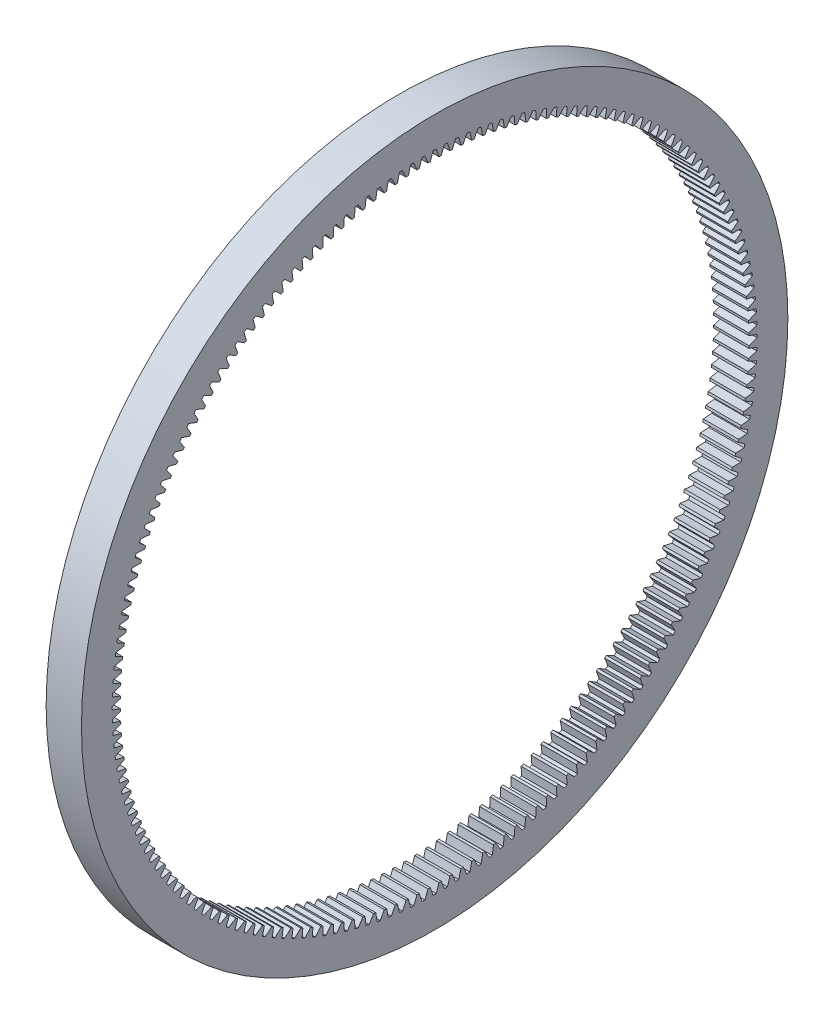
SolidWorks part; units mm, degrees
ref_plane "Plane1" through (0, 0, 0) normal (0, 0, 1) x (1, 0, 0)
ref_plane "Plane2" through (0, 0, 0) normal (0, 1, 0) x (1, 0, 0)
ref_plane "Plane3" through (0, 0, 0) normal (1, 0, 0) x (0, 0, -1)
other "Configuration Table"
sketch "HoldingSke" plane through (0, 0, 0) normal (0, 1, 0) x (1, 0, 0)
  line L0 (0, 0) -> (-1016, 0)
  line L1 (-15, 0) -> (100, 0) construction
  line L2 (0, 0) -> (-2.1039, 2.3779)
  line L3 (0, 0) -> (-11.863, 4.5341)
  line L4 (0, 0) -> (-8.636, 0)
  line L5 (0, 0) -> (-23.7986, -8.8762)
  line L6 (0, 0) -> (-10.5278, -7.1032)
  line L7 (-2.1039, 2.3779) -> (3.3635, 27.1825)
  line L8 (-76.2, 54.61) -> (-54.61, 54.61)
  line L9 (-71.009, 38.7566) -> (-53.1078, 45.2721)
  line L10 (-76.2, 71.12) -> (104.1128, 71.12)
  line L11 (0, 0) -> (-6.35, 0)
  line L12 (-76.2, 101.6) -> (-76.1746, 101.6)
  line L13 (24.9733, 27.94) -> (52.9518, 28.4284)
  line L14 (24.9733, 27.94) -> (25.0241, 27.9398)
  line L15 (24.9733, 27.94) -> (100.4021, 29.52)
  circle A0 centre (0, 0) radius 63.5
  circle A1 centre (0, 0) radius 12.7
  circle A2 centre (0, 0) radius 12.7
  dimension "Num_teeth" = 180
  dimension "Pitch_radius" = 180.3128
  dimension "Width" = 6.35
  dimension "Diameter" = 127
sketch "BasProSke" plane through (0, 0, 0) normal (0, 1, 0) x (1, 0, 0)
  line L0 (-10, 0) -> (60, 0) construction
  line L1 (0, 56.515) -> (0, 63.5)
  line L2 (0, 56.515) -> (6.35, 56.515)
  line L3 (6.35, 56.515) -> (6.35, 63.5)
  line L4 (6.35, 63.5) -> (0, 63.5)
  dimension "Thickness" = 6.35
  dimension "Diameter" = 127
revolve "Base-Revolve" add sketch "BasProSke" angle 360 about L0
sketch "TooCutSke" plane through (0, 0, 0) normal (1, 0, 0) x (0, 0, -1)
  line L3 (0.5622, 57.1472) -> (0.5622, 53.6633) construction
  line L4 (0, 0) -> (0, 59.563) construction
  line L5 (0, 0) -> (-1.1925, 68.3171) construction
  line L6 (-26.4678, 47.8785) -> (36.9935, 48.9862) construction
  circle A0 centre (0, 0) radius 57.15 construction
  circle A1 centre (0, 0) radius 57.9628 construction
  circle A2 centre (0, 0) radius 48.3331 construction
  circle A3 centre (0, 0) radius 56.4896 construction
  arc A4 (0.7806, 56.4842) -> (0.2689, 57.9622) centre (-26.4678, 47.8785) ccw
  arc A5 (0.7806, 56.4842) -> (-0.7806, 56.4842) centre (0, 0) ccw
  arc A6 (0.2689, 57.9622) -> (-0.2689, 57.9622) centre (0, 0) ccw
  arc A7 (-0.2689, 57.9622) -> (-0.7806, 56.4842) centre (26.4678, 47.8785) ccw
extrude "ToothCut" cut sketch "TooCutSke" along normal through all
fillet "Breaks" [suppressed] radius 0.0635
fillet "RootFillets" [suppressed] radius 0.1778
pattern_circular "TeethCuts" count 180 every 2 about axis through (-10, 0, 0) along (1, 0, 0) of "RootFillets", "Breaks", "ToothCut"
equation "' \"Pitch@HoldingSke\" = 4"
equation "' \"Num_teeth@HoldingSke\" = 24"
equation "' \"Ap@HoldingSke\" =  14.5"
equation "' \"Ap@HoldingSke\" = 14.5"
equation "' \"Width@HoldingSke\" = 0.5"
equation "' \"Diameter@HoldingSke\" = 8"
equation "' \"Show_teeth@HoldingSke\" = 100"
equation "' \"Backlash@HoldingSke\" = 0.009"
equation "' \"Addendum_fac@HoldingSke\" = 1.0"
equation "' \"Dedendum_fac@HoldingSke\" = 1.25"
equation "' \"Dedendum_add@HoldingSke\" = 0.00005"
equation "' \"Clearance_fac@HoldingSke\" = 0.25"
equation "\"Overcut_dia@TooCutSke\" = (\"Num_teeth@HoldingSke\" - 2 * \"Addendum_fac@HoldingSke\") / \"Pitch@HoldingSke\" - 0.002"
equation "\"Pitch_dia@TooCutSke\" = \"Num_teeth@HoldingSke\" / \"Pitch@HoldingSke\""
equation "\"Base_dia@TooCutSke\" = \"Num_teeth@HoldingSke\" / \"Pitch@HoldingSke\" * cos((\"Ap@HoldingSke\"  * 3.14159265 / 180)) * 0.90"
equation "\"Root_dia@TooCutSke\" = \"Num_teeth@HoldingSke\"  / \"Pitch@HoldingSke\" + 2 *  \"Dedendum_fac@HoldingSke\"/ \"Pitch@HoldingSke\" + \"Dedendum_add@HoldingSke\" * 2"
equation "\"Half_ang@TooCutSke\" = 180 / \"Num_teeth@HoldingSke\""
equation "\"Half_CT@TooCutSke\" = \"Num_teeth@HoldingSke\" / \"Pitch@HoldingSke\" * sin((3.14159265 / 2 / \"Num_teeth@HoldingSke\")) / 2 + 10 * \"Backlash@HoldingSke\" / 4"
equation "\"Flank_rad@TooCutSke\" = \"Num_teeth@HoldingSke\" / \"Pitch@HoldingSke\" / 4"
equation "\"Radius@RootFillets\"= \"Clearance_fac@HoldingSke\" / \"Pitch@HoldingSke\" + \"Dedendum_add@HoldingSke\""
equation "\"Break_rad@Breaks\" = 0.02 / \"Pitch@HoldingSke\" * 5"
equation "\"Num_teeth@TeethCuts\" = int( \"Show_teeth@HoldingSke\" ) + 1"
equation "\"Num_teeth@TeethCuts\" = ((sgn( \"Num_teeth@TeethCuts\" - \"Num_teeth@HoldingSke\" )-1)*( \"Num_teeth@TeethCuts\" - \"Num_teeth@HoldingSke\" ))/-2+ \"Num_teeth@HoldingSke\""
equation "\"Num_teeth@TeethCuts\" = ((sgn( \"Num_teeth@TeethCuts\" - 2.0)+1)*( \"Num_teeth@TeethCuts\" - 2.0))/2 +2.0"
equation "\"Angle@TeethCuts\" = 360.0 / \"Num_teeth@HoldingSke\""
equation "\"Diameter@BasProSke\" = \"Num_teeth@HoldingSke\"  / \"Pitch@HoldingSke\" + 2 *  \"Dedendum_fac@HoldingSke\"/ \"Pitch@HoldingSke\" + \"Dedendum_add@HoldingSke\" * 2 + 0.002"
equation "\"Diameter@BasProSke\" = ((sgn( \"Diameter@BasProSke\"  - \"Diameter@HoldingSke\" )+1)*( \"Diameter@BasProSke\"  - \"Diameter@HoldingSke\" ))/2 + \"Diameter@HoldingSke\""
equation "\"Inside_diameter@BasProSke\" =  (\"Num_teeth@HoldingSke\" - 2 * \"Addendum_fac@HoldingSke\") / \"Pitch@HoldingSke\" "
equation "\"Thickness@BasProSke\"  = \"Width@HoldingSke\""
